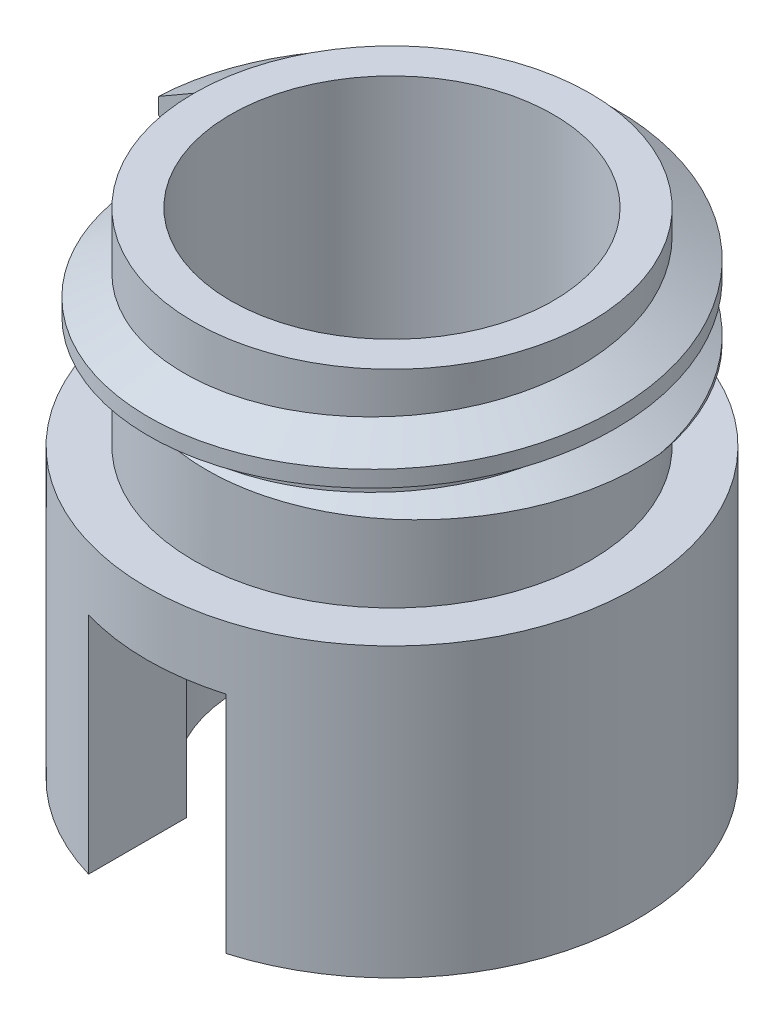
SolidWorks part; units mm, degrees
ref_plane "Front Plane" through (0, 0, 0) normal (0, 0, 1) x (1, 0, 0)
ref_plane "Top Plane" through (0, 0, 0) normal (0, 1, 0) x (1, 0, 0)
ref_plane "Right Plane" through (0, 0, 0) normal (1, 0, 0) x (0, 0, -1)
sketch "Sketch1" plane through (0, 0, 0) normal (0, 1, 0) x (1, 0, 0)
  circle A0 centre (0, 0) radius 2.995
  dimension "D1" = 5.99
extrude "Boss-Extrude1" add sketch "Sketch1" along normal blind 3.52
sketch "Sketch2" plane through (0, 3.52, 0) normal (0, 1, 0) x (1, 0, 0)
  circle A0 centre (0, 0) radius 2.425
  circle A1 centre (0, 0) radius 1.975
  dimension "D1" = 4.85
  dimension "D2" = 3.95
extrude "Boss-Extrude2" add sketch "Sketch2" along normal blind 2.53
thread "Thread1" pitch 0.8 method extrude profile "Thread Profile1" start angle 0, offset 0, length 1.5, pitch 0.8, diameter 4.85
ref_plane "Plane1" through (-2.425, 6.05, 0) normal (0, 0, -1) x (1, 0, 0)
sketch "Thread Profile1" plane through (-2.425, 6.05, 0) normal (0, 0, -1) x (1, 0, 0)
  line L0 (0, 0) -> (0, 0.8) construction
  line L11 (0, 0) -> (0, 0.7)
  line L12 (0, 0.7) -> (-0.433, 0.45)
  line L13 (-0.433, 0.45) -> (-0.433, 0.25)
  line L15 (-0.433, 0.25) -> (0, 0)
  line L17 (-0.433, 0.35) -> (0, 0.35) construction
  point P2 (0, 0)
  dimension "Pitch" = 0.8
  dimension "Profile_Angle" = 60
  dimension "Profile_Land" = 0.2
  dimension "Profile_Height" = 0.433
sketch "Sketch6" plane through (0, 3.52, 0) normal (0, 1, 0) x (1, 0, 0)
  circle A0 centre (0, 0) radius 2.425
  circle A1 centre (0, 0) radius 3.05
extrude "Cut-Extrude1" cut sketch "Sketch6" along normal blind 1.1
sketch "Sketch7" plane through (0, 0, 0) normal (0, -1, 0) x (1, 0, 0)
  circle A0 centre (0, 0) radius 1.875
  dimension "D1" = 3.75
extrude "Cut-Extrude2" cut sketch "Sketch7" against normal blind 3
sketch "Sketch9" plane through (0, 0, 0) normal (0, 0, 1) x (1, 0, 0)
  line L0 (-2.995, 0) -> (2.995, 0) construction
  line L1 (-0.84, 0) -> (0.84, 0)
  line L2 (-0.84, 0) -> (-0.84, 2.75)
  line L3 (-0.84, 2.75) -> (0.84, 2.75)
  line L4 (0.84, 0) -> (0.84, 2.75)
  point P6 (0, 2.75)
  dimension "D1" = 0
  dimension "D2" = 1.68
  dimension "D3" = 2.75
extrude "Cut-Extrude4" cut sketch "Sketch9" against normal through all both and the other way through all
sketch "Sketch10" plane through (0, 6.05, 0) normal (0, 1, 0) x (1, 0, 0)
  circle A0 centre (0, 0) radius 1.975
extrude "Cut-Extrude6" cut sketch "Sketch10" against normal blind 3.18
